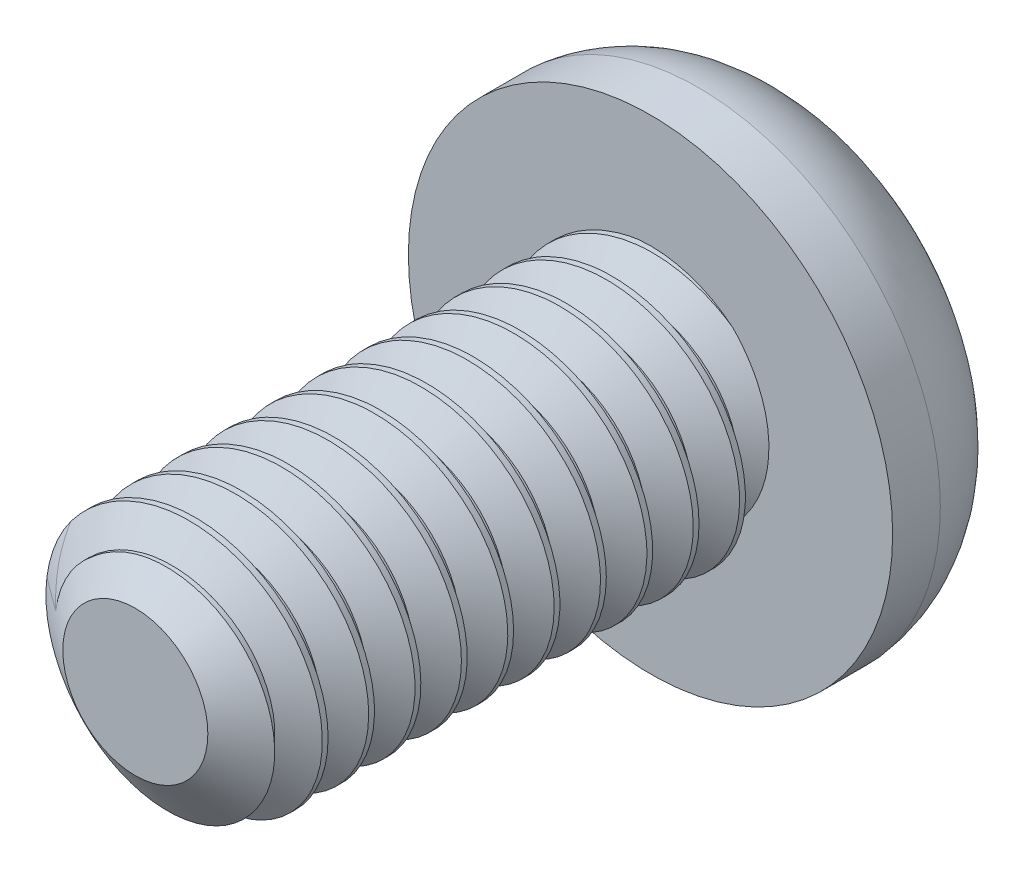
SolidWorks part; units mm, degrees
material "AISI 1015 Steel, Cold Drawn (SS)"
ref_plane "Front Plane" through (0, 0, 0) normal (0, 0, 1) x (1, 0, 0)
ref_plane "Top Plane" through (0, 0, 0) normal (0, 1, 0) x (1, 0, 0)
ref_plane "Right Plane" through (0, 0, 0) normal (1, 0, 0) x (0, 0, -1)
sketch "Sketch1" plane through (0, 0, 0) normal (0, 0, 1) x (1, 0, 0)
  circle A0 centre (0, 0) radius 1.25
  dimension "OD" = 2.5
extrude "Extrude1" add sketch "Sketch1" against normal blind 5
sketch "Sketch2" plane through (0, 0, 0) normal (0, 0, 1) x (1, 0, 0)
  circle A0 centre (0, 0) radius 1.25 construction
  circle A1 centre (0, 0) radius 1.25
curve "Helix/Spiral1" pitch 0.45 height 5.45 radius 1.25 centre (0, 0, 0) axis (0, 0, -1) start towards (0, 1, 0) parameters "pitch"=0.45
sketch "Sketch3" plane through (0, 0, 0) normal (1, 0, 0) x (0, 0, -1)
  line L0 (-0.3937, 1.25) -> (-0.225, 0.9577)
  line L1 (-0.225, 0.9577) -> (-0.1687, 0.9577)
  line L2 (-0.1687, 0.9577) -> (0, 1.25)
  line L3 (-0.3937, 1.25) -> (0, 1.25)
  line L4 (-0.1969, 1.25) -> (-0.1969, 0.9577) construction
  line L5 (-0.3094, 1.1039) -> (-0.0844, 1.1039) construction
  line L6 (0, 1.25) -> (0, -1.25) construction
  dimension "D1" = 0.0563
  dimension "D2" = 0.225
  dimension "D3" = 60
sweep "Cut-Sweep1" cut profiles "Sketch3" path "Helix/Spiral1"
sketch "Sketch4" plane through (0, 0, 0) normal (1, 0, 0) x (0, 0, -1)
  line L0 (0.3825, 1.25) -> (0, 0.7037)
  line L1 (0, 0.7037) -> (0, 1.25)
  line L2 (0.3825, 1.25) -> (0, 1.25)
  line L3 (-0.3937, 1.25) -> (0, 1.25) construction
  line L4 (0, 0) -> (7.0209, 0) construction
  dimension "D1" = 55
  dimension "D2" = 0.254
revolve "Cut-Revolve1" cut sketch "Sketch4" angle 360 about L4
sketch "Sketch6" plane through (0, 0, -5) normal (0, 0, -1) x (-1, 0, 0)
  circle A0 centre (0, 0) radius 2.35
  dimension "head dia" = 4.7
extrude "Extrude2" add sketch "Sketch6" along normal blind 1.5
sketch "Sketch10" plane through (0, 0, 0) normal (1, 0, 0) x (0, 0, -1)
  line L0 (6.5, -2.35) -> (6.5, 2.35) construction
  line L1 (0, 0) -> (15.9584, 0) construction
  line L2 (6.5, 2.35) -> (5, 2.35) construction
  line L3 (5, 2.35) -> (5, -2.35) construction
  line L4 (5.225, 2.35) -> (5.225, 2.85)
  line L5 (5.225, 2.85) -> (7, 2.85)
  line L6 (7, 2.85) -> (7, 1.2)
  line L7 (6.5, 1.2) -> (7, 1.2)
  arc A0 (6.5, 1.2) -> (5.225, 2.35) centre (5.3439, 1.2) ccw
  dimension "D1" = 2.4
  dimension "D2" = 0.225
  dimension "D3" = 0.5
revolve "Cut-Revolve2" cut sketch "Sketch10" angle 360 about L1
ref_plane "Plane1" through (0, 0, -6.125) normal (0, 0, 1) x (1, 0, 0)
sketch "Sketch7" plane through (0, 0, -6.5) normal (0, 0, -1) x (-1, 0, 0)
  line L0 (0, 0) -> (-1.0392, -0.6)
  line L1 (0, 0) -> (-1.0392, 0.6)
  line L2 (0, 0) -> (0.3286, 0) construction
  circle A0 centre (0, 0) radius 1.2 construction
  circle A1 centre (0, 0) radius 1.056 construction
  circle A2 centre (0, 0) radius 0.9 construction
  arc A3 (-1.0347, 0.4487) -> (-1.0392, 0.6) centre (-0.9145, 0.528) cw
  arc A4 (-1.0347, -0.4487) -> (-1.0392, -0.6) centre (-0.9145, -0.528) ccw
  arc A5 (-1.0347, 0.4487) -> (-1.0347, -0.4487) centre (-1.7146, 0) cw
  dimension "D1" = 2.112
  dimension "torx dia" = 2.4
  dimension "D2" = 1.8
  dimension "D3" = 60
extrude "Cut-Extrude1" cut sketch "Sketch7" against normal blind 1.125
pattern_circular "CirPattern1" count 6 over 360 about axis through (0, 0, 0) along (0, 0, -1) of "Cut-Extrude1"
sketch "Sketch8" plane through (0, 0, -6.5) normal (0, 0, 1) x (1, 0, 0)
  circle A0 centre (0, 0) radius 1.2 construction
  circle A1 centre (0, 0) radius 1.2
extrude "Cut-Extrude2" cut sketch "Sketch8" along normal blind 1.125 draft 45
sketch "Sketch9" plane through (0, 0, 0) normal (1, 0, 0) x (0, 0, -1)
  line L0 (0, 1.25) -> (0, -1.25) construction
  line L1 (2.475, 1.25) -> (2.475, -1.25) construction
  dimension "D1" = 2.475
sketch "Sketch12" plane through (0, 0, 0) normal (1, 0, 0) x (0, 0, -1)
  line L0 (5.375, 0) -> (5.375, 1.2)
  line L1 (5.375, 0) -> (5, 0)
  line L2 (5, 0) -> (5, 1.6231) construction
  line L3 (5, 0) -> (18.6803, 0) construction
  line L4 (6.5, 2.3278) -> (6.5, -0.613) construction
  line L5 (6.5, 1.2) -> (6.5, 0.6) construction
  arc A0 (5, 0) -> (5.375, 1.2) centre (7.1075, 0) cw
  dimension "D1" = 0.375
  dimension "D2" = 2.4
  dimension "D3" = 1.125
revolve "Cut-Revolve3" cut sketch "Sketch12" angle 360 about L3
sketch "Sketch13" plane through (0, 0, -5.375) normal (0, 0, 1) x (1, 0, 0)
  arc A4 (1.0347, 0.4487) -> (1.0392, 0.6) centre (0.9145, 0.528) ccw
  arc A5 (1.0347, 0.4487) -> (1.0347, -0.4487) centre (1.7146, 0) ccw
  arc A6 (1.0392, -0.6) -> (1.0347, -0.4487) centre (0.9145, -0.528) ccw
  arc A7 (1.0392, -0.6) -> (1.0392, 0.6) centre (0, 0) ccw
  arc A8 (1.0347, 0.4487) -> (1.0392, 0.6) centre (0.9145, 0.528) ccw
  arc A9 (1.0347, 0.4487) -> (1.0347, -0.4487) centre (1.7146, 0) ccw
  arc A10 (1.0392, -0.6) -> (1.0347, -0.4487) centre (0.9145, -0.528) ccw
  arc A11 (1.0392, -0.6) -> (1.0392, 0.6) centre (0, 0) ccw
  dimension "D1" = 0
extrude "Extrude3" add sketch "Sketch13" along normal up to next
pattern_circular "CirPattern2" count 6 over 360 about axis through (0, 0, -5) along (0, 0, 1) of "Extrude3"
equation "\"D3@Helix/Spiral1\" = \"screw length@Extrude1\"+\"pitch@Helix/Spiral1\""
equation "\"D1@Sketch3\" = \"pitch@Helix/Spiral1\"*.125"
equation "\"D2@Sketch3\" = \"pitch@Helix/Spiral1\"*.5"
equation "\"D1@Sketch9\" = \"pitch@Helix/Spiral1\"*5.5"
equation "\"D1@Sketch10\" =\"torx dia@Sketch7\""
equation "\"D1@Plane1\" = \"head depth@Extrude2\"*.75"
equation "\"D1@Sketch7\" = \"torx dia@Sketch7\"*.88"
equation "\"D2@Sketch7\" = \"torx dia@Sketch7\"*.75"
equation "\"D1@Cut-Extrude1\" = \"head depth@Extrude2\"*.75"
equation "\"D1@Cut-Extrude2\" = \"head depth@Extrude2\"*.750"
equation "\"D1@Sketch12\" = \"head depth@Extrude2\"*.25"
equation "\"D2@Sketch12\" = \"torx dia@Sketch7\""
equation "\"D3@Sketch12\" = \"head depth@Extrude2\"*.750"
equation "\"D2@Sketch10\" = \"head depth@Extrude2\"*.15"
